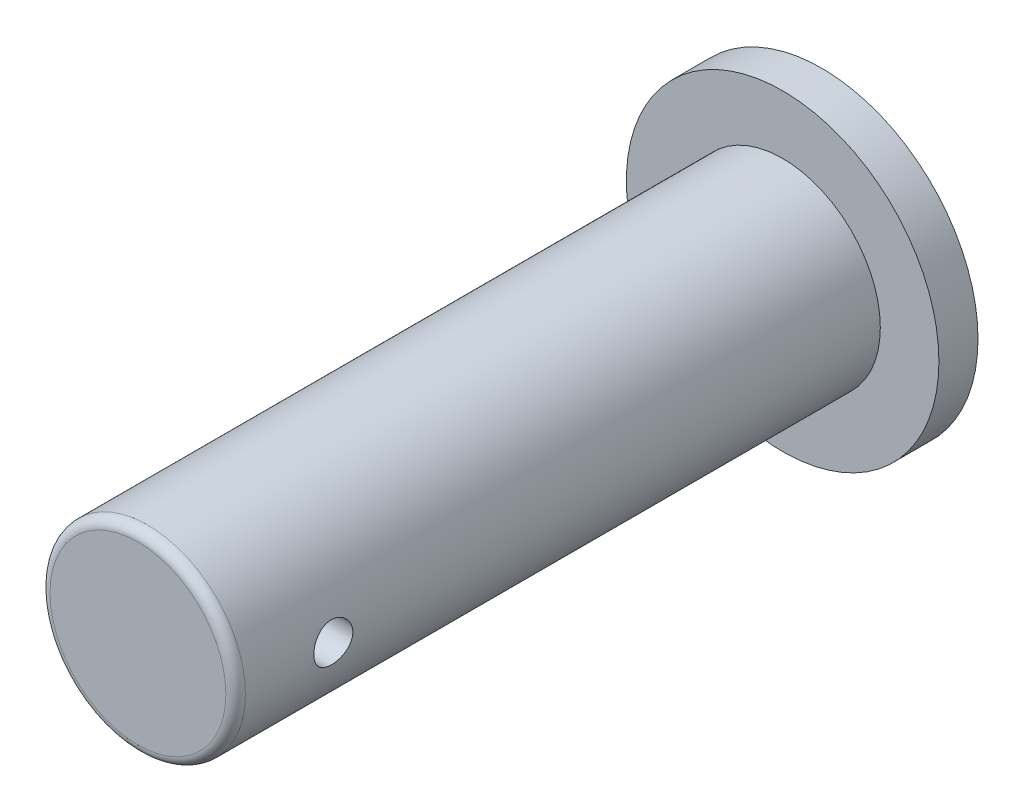
SolidWorks part; units mm, degrees
ref_plane "Front Plane" through (0, 0, 0) normal (0, 0, 1) x (1, 0, 0)
ref_plane "Top Plane" through (0, 0, 0) normal (0, 1, 0) x (1, 0, 0)
ref_plane "Right Plane" through (0, 0, 0) normal (1, 0, 0) x (0, 0, -1)
sketch "Sketch1" plane through (0, 0, 0) normal (0, 0, 1) x (1, 0, 0)
  circle A0 centre (0, 0) radius 5
  circle A1 centre (0, 0) radius 8
extrude "Boss-Extrude1" add sketch "Sketch1" along normal blind 35 contours A0
extrude "Boss-Extrude2" add sketch "Sketch1<3>" along normal blind 2
sketch "Sketch1<3>" plane through (0, 0, 0) normal (0, 0, 1) x (1, 0, 0) same geometry as "Sketch1"
sketch "Sketch3" plane through (0, 0, 0) normal (1, 0, 0) x (0, 0, -1)
  line L0 (-39.0966, 0) -> (5.1669, 0) construction
  line L1 (-35, 5) -> (-35, -5) construction
  circle A0 centre (-30, 0) radius 1
  dimension "D1" = 5
extrude "Cut-Extrude3" cut sketch "Sketch3" against normal through all and the other way through all
fillet "Fillet1" radius 0.5 1 edges at (5, 0, 35)
